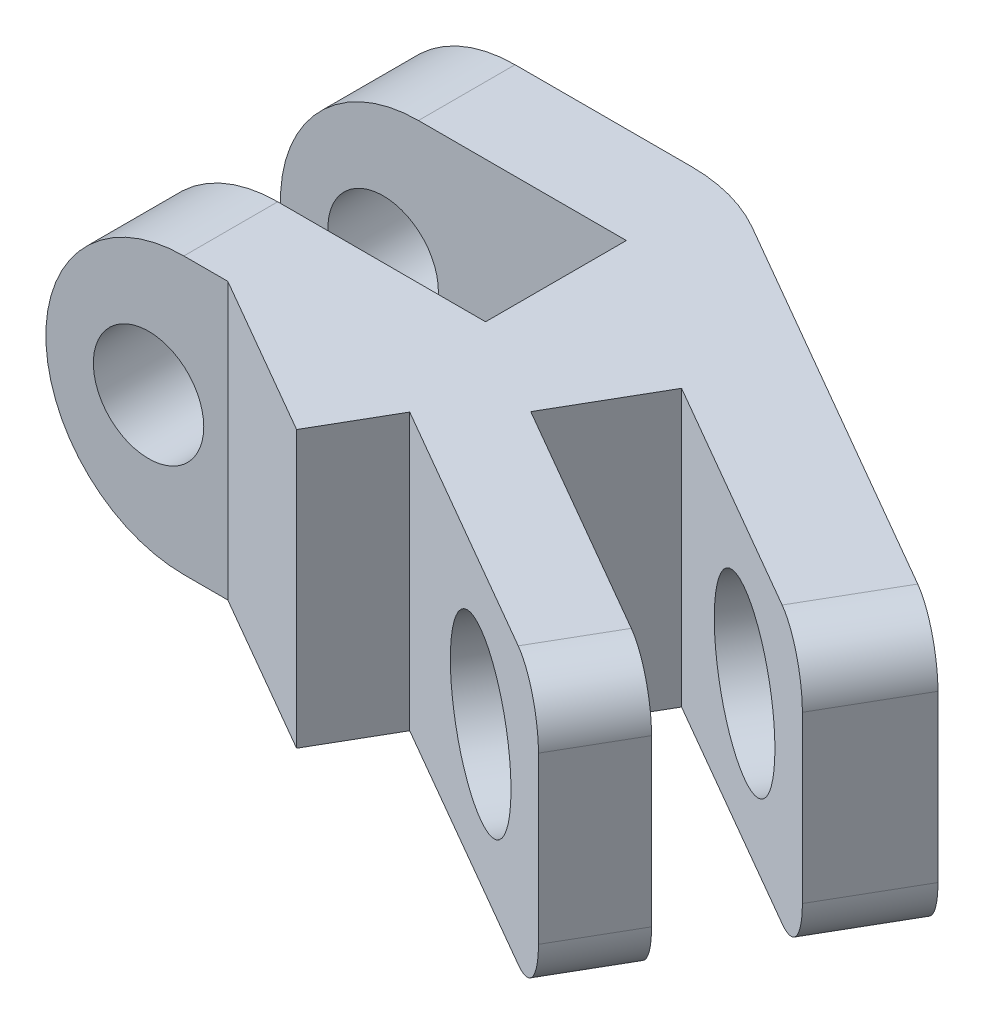
SolidWorks part; units mm, degrees
ref_plane "前视基准面" through (0, 0, 0) normal (0, 0, 1) x (1, 0, 0)
ref_plane "上视基准面" through (0, 0, 0) normal (0, 1, 0) x (1, 0, 0)
ref_plane "右视基准面" through (0, 0, 0) normal (1, 0, 0) x (0, 0, -1)
sketch "草图1" plane through (0, 0, 0) normal (0, 0, 1) x (1, 0, 0)
  circle A0 centre (0, 0) radius 2.5
extrude "凸台-拉伸1" add sketch "草图1" along normal blind 6
sketch "草图2" plane through (0, 0, 0) normal (0, 0, -1) x (-1, 0, 0)
  line L1 (0, -2.5) -> (-4, -2.5)
  line L2 (0, -2.5) -> (0, 2.5)
  line L3 (0, 2.5) -> (-4, 2.5)
  line L4 (-4, -2.5) -> (-4, 2.5)
  circle A0 centre (0, 0) radius 2.5 construction
extrude "凸台-拉伸2" add sketch "草图2" against normal up to surface (6 mm away) up to face at (2.5, 0, 6)
ref_plane "基准面8" through (0, 0, 0) normal (1, 0, 0) x (0, 0, -1)
sketch "草图11" plane through (0, 0, 0) normal (1, 0, 0) x (0, 0, -1)
  line L0 (-3, 2.5) -> (-3, -2.5) construction
  line L1 (-6, 2.5) -> (0, 2.5) construction
  line L2 (-6, -2.5) -> (0, -2.5) construction
ref_plane "基准面4" through (1, 0, -1.7321) normal (0.5, 0, -0.866) x (0, -1, 0)
ref_plane "基准面5" through (0, 0, 3) normal (0, 0, 1) x (1, 0, 0)
ref_plane "基准面9" through (-1.299, 0, 2.25) normal (-0.5, 0, 0.866) x (0, -1, 0)
ref_plane "基准面10" through (-0.399, 0, 0.6912) normal (-0.5, 0, 0.866) x (0, -1, 0)
sketch "草图13" plane through (-0.399, 0, 0.6912) normal (-0.5, 0, 0.866) x (0, -1, 0)
  line L1 (-2.5, 3.4641) -> (2.5, 3.4641) construction
  line L2 (-2.5, 3.4641) -> (2.5, 3.4641)
  line L6 (2.5, 3.4641) -> (2.5, 13.4641)
  line L7 (2.5, 13.4641) -> (-2.5, 13.4641)
  line L8 (-2.5, 13.4641) -> (-2.5, 3.4641)
extrude "凸台-拉伸4" add sketch "草图13" against normal up to vertex (2.7981 mm away) and the other way blind 4 up to point (4, -2.5, 0)
sketch "草图14" plane through (-0.399, 0, 0.6912) normal (-0.5, 0, 0.866) x (0, -1, 0)
  line L0 (2.5, 13.4641) -> (-2.5, 13.4641) construction
  line L1 (2.5, 13.4641) -> (-2.5, 13.4641) construction
  line L8 (-2.5, 13.4641) -> (-2.5, 7.4865)
  line L9 (-2.5, 7.4865) -> (2.5, 7.4865)
  line L10 (2.5, 7.4865) -> (2.5, 13.4641)
  line L11 (2.5, 13.4641) -> (-2.5, 13.4641)
extrude "切除-拉伸6" cut sketch "草图14" against normal blind 1 and the other way blind 1
sketch "草图5" plane through (0, 0, 6) normal (0, 0, 1) x (1, 0, 0)
  line L0 (-2.5, 0) -> (1.3929, 0) construction
  arc A0 (0, 2.5) -> (0, -2.5) centre (0, 0) ccw construction
  circle A1 centre (-0.6397, 0) radius 1
extrude "切除-拉伸2" cut sketch "草图5" against normal through all
sketch "草图6" plane through (0, 0, 3) normal (0, 0, 1) x (1, 0, 0)
  line L7 (3.7657, 2.5) -> (0, 2.5)
  line L8 (0, -2.5) -> (3.7657, -2.5)
  line L10 (3.7657, -2.5) -> (3.7657, 2.5)
  arc A2 (0, 2.5) -> (0, -2.5) centre (0, 0) ccw
extrude "切除-拉伸3" cut sketch "草图6" against normal blind 1.25 and the other way blind 1.3
fillet "圆角2" radius 3 1 edges at (4, 0, 0)
sketch "草图15" plane through (1, 0, -1.7321) normal (0.5, 0, -0.866) x (-0.866, 0, -0.5)
  line L0 (-13.4641, 0) -> (-9.5112, 0) construction
  line L1 (-13.4641, -2.5) -> (-13.4641, 2.5) construction
  circle A0 centre (-10.6057, 0) radius 1.5
extrude "切除-拉伸7" cut sketch "草图15" against normal through all both and the other way through all
fillet "圆角3" radius 1 4 edges at (10.0112, -2.5, 9.5883) (10.0112, 2.5, 9.5883) (12.2107, 2.5, 5.7786) (12.2107, -2.5, 5.7786)
sketch "草图18" plane through (-2.399, 0, 4.1553) normal (-0.5, 0, 0.866) x (0.866, 0, 0.5)
  line L1 (13.4641, 2.5) -> (7.0938, 2.5)
  line L2 (13.4641, 2.5) -> (13.4641, -2.7887)
  line L3 (13.4641, -2.7887) -> (7.0938, -2.7887)
  line L4 (7.0938, 2.5) -> (7.0938, -2.7887)
extrude "切除-拉伸9" cut sketch "草图18" against normal blind 1.5
